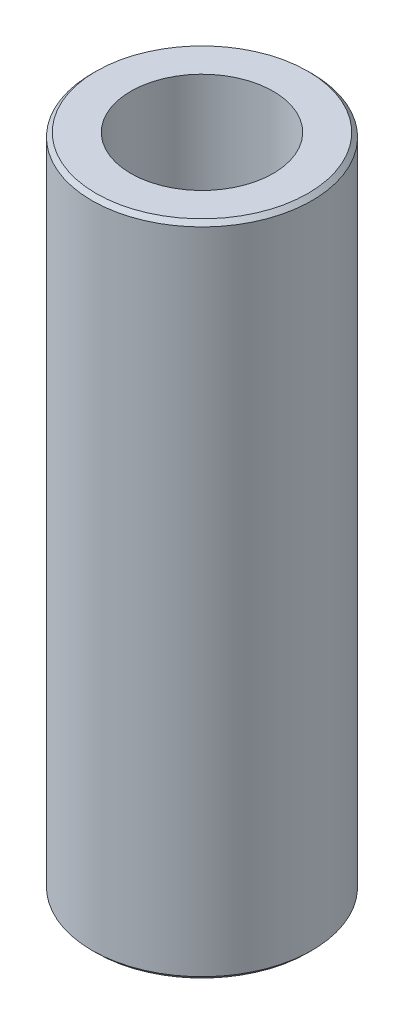
SolidWorks part; units mm, degrees
ref_plane "Front Plane" through (0, 0, 0) normal (0, 0, 1) x (1, 0, 0)
ref_plane "Top Plane" through (0, 0, 0) normal (0, 1, 0) x (1, 0, 0)
ref_plane "Right Plane" through (0, 0, 0) normal (1, 0, 0) x (0, 0, -1)
sketch "Sketch1" plane through (0, 0, 0) normal (0, 1, 0) x (1, 0, 0)
  circle A0 centre (0, 0) radius 17.5
  dimension "SHAFT_OD" = 35
extrude "Boss-Extrude1" add sketch "Sketch1" along normal blind 104.5924
sketch "Sketch2" plane through (0, 0, 0) normal (0, 1, 0) x (1, 0, 0)
  circle A0 centre (0, 0) radius 11.3309
  dimension "BORE_D" = 22.6618
extrude "Cut-Extrude1" cut sketch "Sketch2" along normal through all
chamfer "Chamfer1" distance 0.6567 angle 45 2 edges at (0, 104.5924, 17.5) (0, 0, 17.5)
